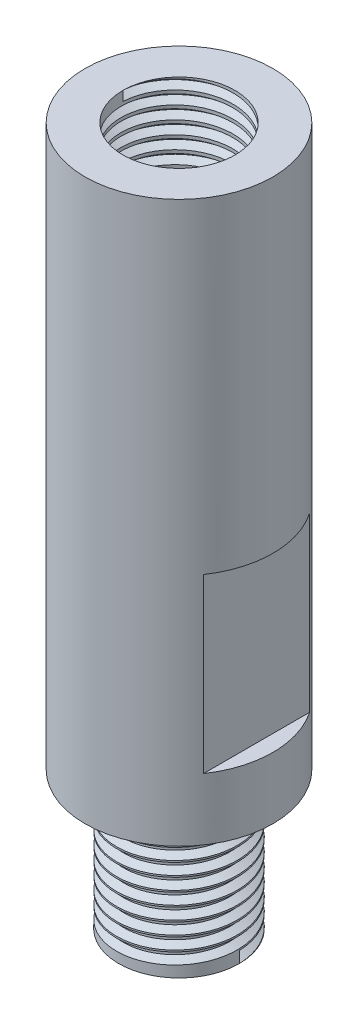
SolidWorks part; units mm, degrees
ref_plane "Front Plane" through (0, 0, 0) normal (0, 0, 1) x (1, 0, 0)
ref_plane "Top Plane" through (0, 0, 0) normal (0, 1, 0) x (1, 0, 0)
ref_plane "Right Plane" through (0, 0, 0) normal (1, 0, 0) x (0, 0, -1)
sketch "Sketch1" plane through (0, 0, 0) normal (0, 1, 0) x (1, 0, 0)
  circle A0 centre (0, 0) radius 10.9
  dimension "D1" = 21.8
extrude "Boss-Extrude1" add sketch "Sketch1" along normal blind 65
sketch "Sketch2" plane through (0, 65, 0) normal (0, 1, 0) x (1, 0, 0)
  circle A0 centre (0, 0) radius 6.5
  dimension "D1" = 13
extrude "Cut-Extrude1" cut sketch "Sketch2" against normal blind 20
thread "Thread1" pitch 1.5 method cut profile "Thread Profile1" start angle 0, offset 0, length 26, pitch 1.5, diameter 13
ref_plane "Plane1" through (-6.5, 65, 0) normal (0, 0, 1) x (-1, 0, 0)
sketch "Thread Profile1" plane through (-6.5, 65, 0) normal (0, 0, 1) x (-1, 0, 0)
  line L0 (0, 0) -> (0, 1.5) construction
  line L1 (0, 0) -> (0.8119, 0.4687)
  line L2 (0.8119, 0.4687) -> (0.8119, 0.6562)
  line L3 (0.8119, 0.6562) -> (0, 1.125)
  line L4 (0.8119, 0.5625) -> (0, 0.5625) construction
  line L11 (0, 0) -> (0, 1.125)
  point P2 (0, 0)
  dimension "Pitch" = 1.5
  dimension "Profile_Angle" = 60
  dimension "Profile_Land" = 0.1875
  dimension "Profile_Height" = 0.8119
sketch "Sketch8" plane through (0, 0, 0) normal (0, -1, 0) x (1, 0, 0)
  circle A0 centre (0, 0) radius 7
  dimension "D1" = 14
extrude "Boss-Extrude2" add sketch "Sketch8" along normal blind 16
thread "Thread2" pitch 1.5 method cut profile "Thread Profile2" start angle 0, offset 0, length 14, pitch 1.5, diameter 14
ref_plane "Plane2" through (7, -16, 0) normal (0, 0, 1) x (1, 0, 0)
sketch "Thread Profile2" plane through (7, -16, 0) normal (0, 0, 1) x (1, 0, 0)
  line L0 (0, 0) -> (0, 1.5) construction
  line L11 (0, 0) -> (0, 1.3125)
  line L12 (0, 1.3125) -> (-0.8119, 0.8437)
  line L13 (-0.8119, 0.8437) -> (-0.8119, 0.4687)
  line L15 (-0.8119, 0.4687) -> (0, 0)
  line L17 (-0.8119, 0.6562) -> (0, 0.6562) construction
  point P2 (0, 0)
  dimension "Pitch" = 1.5
  dimension "Profile_Angle" = 60
  dimension "Profile_Land" = 0.375
  dimension "Profile_Height" = 0.8119
sketch "Sketch23" plane through (0, 0, 0) normal (0, 0, 1) x (1, 0, 0)
  line L0 (-10.9, 65) -> (-10.9, 0) construction
  line L1 (-10.9, 7) -> (-9, 7)
  line L2 (-10.9, 7) -> (-10.9, 27)
  line L3 (-10.9, 27) -> (-9, 27)
  line L4 (-9, 7) -> (-9, 27)
  line L5 (10.9, 0) -> (10.9, 65) construction
  line L6 (10.9, 7.1749) -> (9, 7.1749)
  line L7 (10.9, 7.1749) -> (10.9, 27.1749)
  line L8 (10.9, 27.1749) -> (9, 27.1749)
  line L9 (9, 7.1749) -> (9, 27.1749)
  dimension "D1" = 20
  dimension "D2" = 7
  dimension "D3" = 18
  dimension "D4" = 1.9
  dimension "D5" = 1.9
extrude "Cut-Extrude2" cut sketch "Sketch23" against normal blind 16 and the other way blind 16
